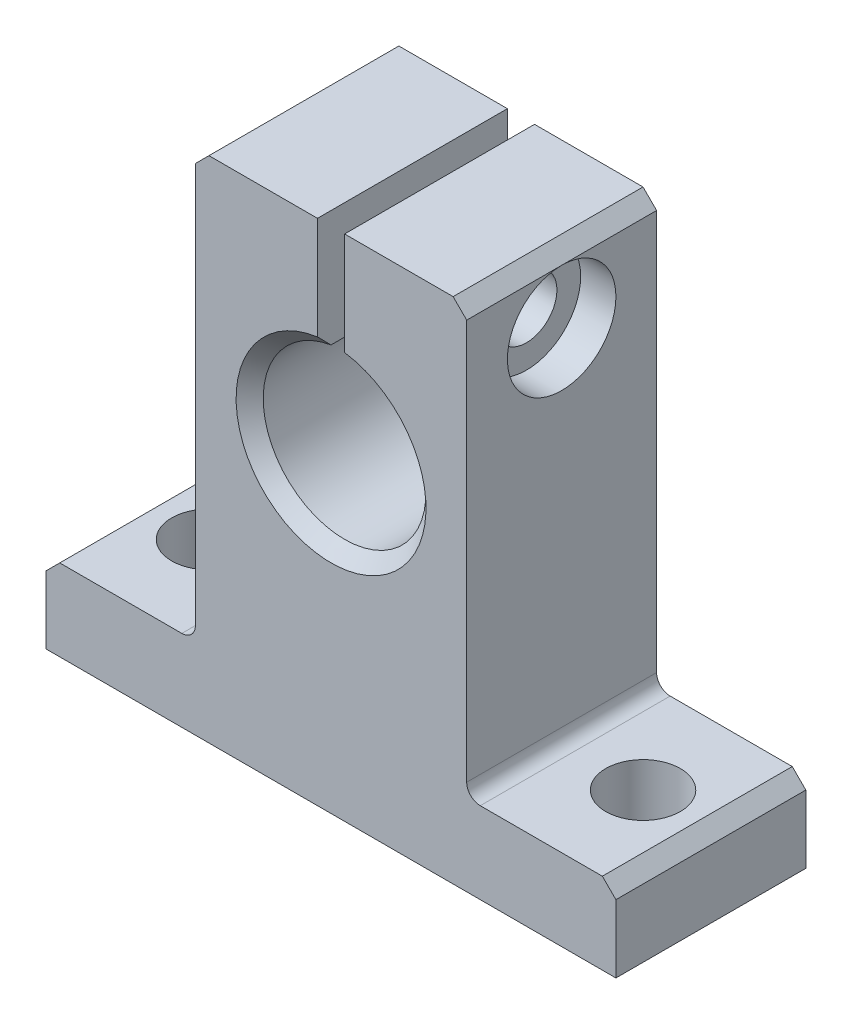
SolidWorks part; units mm, degrees
material "Lega 1060"
ref_plane "Piano frontale" through (0, 0, 0) normal (0, 0, 1) x (1, 0, 0)
ref_plane "Piano superiore" through (0, 0, 0) normal (0, 1, 0) x (1, 0, 0)
ref_plane "Piano destro" through (0, 0, 0) normal (1, 0, 0) x (0, 0, -1)
ref_plane "Piano1" through (0, 0, -7) normal (0, 0, -1) x (-1, 0, 0)
sketch "Schizzo10" plane through (0, 0, 0) normal (0, 0, 1) x (1, 0, 0)
  line L0 (21, 0) -> (-21, 0)
  line L1 (-21, 0) -> (-21, 6)
  line L2 (-21, 6) -> (-10, 6)
  line L3 (-10, 6) -> (-10, 37.5)
  line L4 (-10, 37.5) -> (-1, 37.5)
  line L5 (-1, 37.5) -> (-1, 28.9161)
  line L6 (0, -6.3586) -> (0, 69.8144) construction
  line L7 (1, 37.5) -> (1, 28.9161)
  line L8 (10, 37.5) -> (1, 37.5)
  line L9 (10, 6) -> (10, 37.5)
  line L10 (21, 6) -> (10, 6)
  line L11 (21, 0) -> (21, 6)
  arc A0 (-1, 28.9161) -> (1, 28.9161) centre (0, 23) ccw
  point P13 (0, 0)
  dimension "D1" = 12
  dimension "D2" = 42
  dimension "D3" = 6
  dimension "D4" = 20
  dimension "D5" = 23
  dimension "D6" = 37.5
  dimension "D7" = 2
extrude "Estrusione-Estrusione2" add sketch "Schizzo10" along normal blind 14
hole_wizard "Foro Ø5.5 (5.5)-3" positions "Schizzo12" profile "Schizzo11" hole size "Ø5.5" standard "ISO" end condition through all
sketch "Schizzo12" plane through (0, 6, 0) normal (0, 1, 0) x (1, 0, 0)
  line L0 (-17.0222, -7) -> (18.382, -7) construction
  line L2 (-10, 0) -> (-21, 0) construction
  line L3 (-10, -14) -> (-21, -14) construction
  point P0 (-16, -7)
  point P2 (16, -7)
  dimension "D1" = 32
  dimension "D2" = 16
sketch "Schizzo11" plane through (-16, 6, 7) normal (1, 0, 0) x (0, 0, 1)
  line L0 (0, 0) -> (0, 6)
  line L1 (0, 6) -> (2.75, 6)
  line L2 (2.75, 6) -> (2.75, 0)
  line L5 (2.75, 0) -> (0, 0)
  line L11 (0, -6.35) -> (0, 107.95) construction
  dimension "Thru Hole Dia." = 5.5
  dimension "Thru Hole Depth" = 6
hole_wizard "Foro lamato per Vite M4 a testa cilindrica piana-1" positions "Schizzo14" profile "Schizzo13" counterbore size "M4" standard "ISO" end condition up to next
sketch "Schizzo14" plane through (10, 0, 0) normal (1, 0, 0) x (0, 0, -1)
  line L0 (-7, 20.4964) -> (-7, 29.1822) construction
  line L2 (-14, 6) -> (-14, 37.5) construction
  line L3 (0, 6) -> (0, 37.5) construction
  line L4 (-14, 37.5) -> (0, 37.5) construction
  point P0 (-7, 32.5)
  dimension "D1" = 5
sketch "Schizzo13" plane through (10, 32.5, 7) normal (0, 1, 0) x (0, 0, -1)
  line L0 (0, 0) -> (0, 9)
  line L1 (0, 9) -> (2.25, 9)
  line L3 (2.25, 9) -> (2.25, 2.6)
  line L4 (2.25, 2.6) -> (4, 2.6)
  line L5 (4, 2.6) -> (4, 0)
  line L7 (4, 0) -> (0, 0)
  line L11 (0, -6.35) -> (0, 107.95) construction
  dimension "Thru Hole Dia." = 4.5
  dimension "Thru Hole Depth" = 9
  dimension "C'Bore Dia." = 8
  dimension "C'Bore Depth" = 2.6
hole_wizard "Foro filettato M4-1" positions "Schizzo16" profile "Schizzo15" tap size "M4" standard "ISO" end condition through all
sketch "Schizzo16" plane through (-1, 0, 0) normal (1, 0, 0) x (0, 0, -1)
  circle A0 centre (-7, 32.5) radius 2.25 construction
  point P0 (-7, 32.5)
sketch "Schizzo15" plane through (-1, 32.5, 7) normal (0, 1, 0) x (0, 0, -1)
  line L0 (0, 0) -> (0, 20)
  line L1 (0, 20) -> (1.65, 20)
  line L2 (1.65, 20) -> (1.65, 0.2165)
  line L3 (1.65, 0.2165) -> (2.025, 0)
  line L5 (2.025, 0) -> (0, 0)
  line L6 (-1.65, 0.2165) -> (-2.025, 0) construction
  line L11 (0, -6.35) -> (0, 107.95) construction
  dimension "Thread Major Dia." = 3.3
  dimension "Thru Tap Drill Depth" = 20
  dimension "Near C'Sink Dia." = 4.05
  dimension "Near C'Sink Angle" = 120
fillet "Raccordo1" radius 1 2 edges at (-10, 6, 7) (10, 6, 7)
chamfer "Smusso1" distance 1 angle 45 6 edges at (0, 17, 0) (0, 17, 14) (-10, 37.5, 7) (10, 37.5, 7) (-21, 6, 7) (21, 6, 7)
